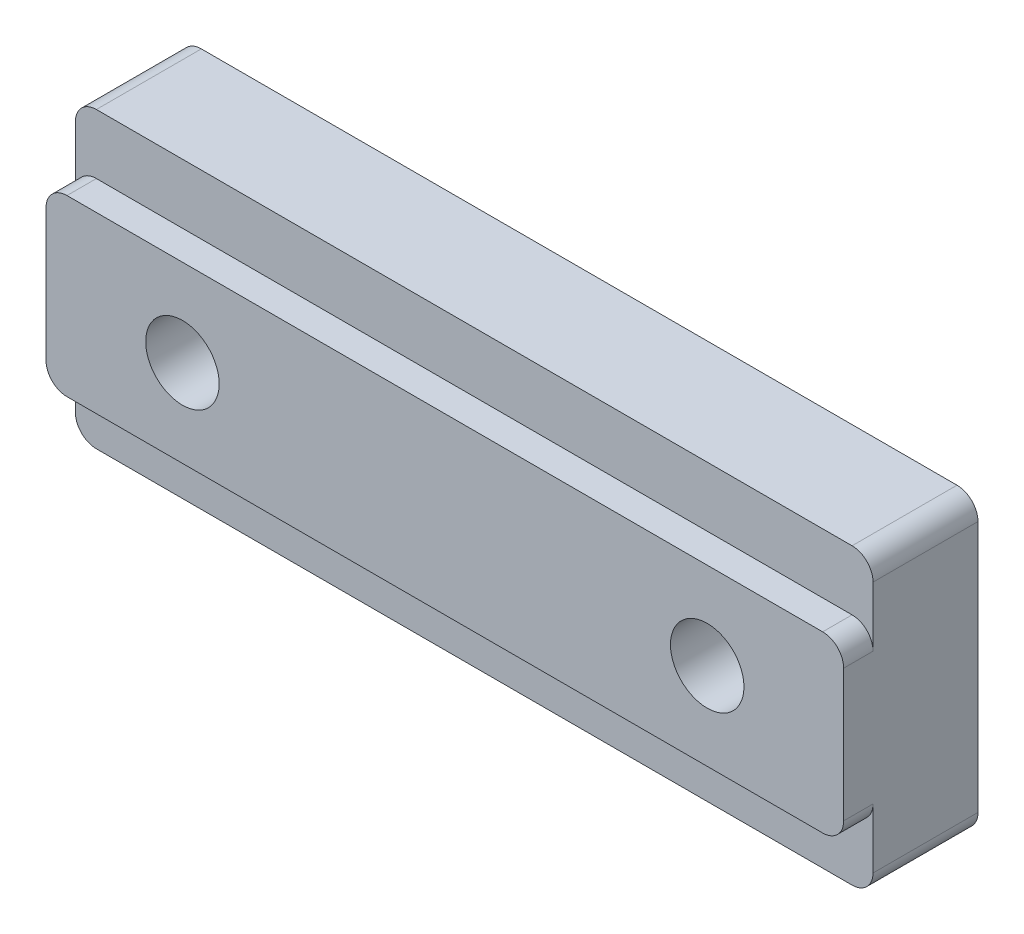
SolidWorks part; units mm, degrees
ref_plane "Спереди" through (0, 0, 0) normal (0, 0, 1) x (1, 0, 0)
ref_plane "Сверху" through (0, 0, 0) normal (0, 1, 0) x (1, 0, 0)
ref_plane "Справа" through (0, 0, 0) normal (1, 0, 0) x (0, 0, -1)
sketch "Эскиз1" plane through (0, 0, 0) normal (0, 0, 1) x (1, 0, 0)
  line L0 (-25.5909, 0) -> (25.8391, 0) construction
  line L1 (-19, -7) -> (19, -7)
  line L2 (-19, -7) -> (-19, 7)
  line L3 (-19, 7) -> (19, 7)
  line L4 (19, -7) -> (19, 7)
  line L5 (-19, -7) -> (19, 7) construction
  line L6 (-19, 7) -> (19, -7) construction
  line L7 (0, 11.0918) -> (0, -11.9823) construction
  line L9 (-19, -4.15) -> (19, -4.15)
  line L10 (-19, -4.15) -> (-19, 4.15)
  line L11 (-19, 4.15) -> (19, 4.15)
  line L12 (19, -4.15) -> (19, 4.15)
  line L13 (-19, -4.15) -> (19, 4.15) construction
  line L14 (-19, 4.15) -> (19, -4.15) construction
  circle A0 centre (-12.5, 0) radius 1.75
  circle A1 centre (12.5, 0) radius 1.75
  point P0 (0, 0)
  point P14 (0, 0)
  dimension "D1" = 12.5
  dimension "D3" = 3.5
  dimension "D4" = 3.5
  dimension "D2" = 8.3
extrude "Бобышка-Вытянуть1" add sketch "Эскиз1" along normal blind 5 contours L9 L2 L1 L4 | L11 L2 L9 L4 A0 A1 | L2 L11 L4 L3 region at (0, -5.575, 0) region at (0, 0, 0) region at (0, 5.575, 0)
extrude "Бобышка-Вытянуть2" add sketch "Эскиз1<3>" along normal blind 6.4 contours L11 L2 L9 L4 A0 A1 region at (0, 0, 0)
sketch "Эскиз1<3>" plane through (0, 0, 0) normal (0, 0, 1) x (1, 0, 0) same geometry as "Эскиз1"
sketch "Эскиз2" plane through (0, 0, 0) normal (0, 0, -1) x (-1, 0, 0)
  line L0 (0, 9.4717) -> (0, -10.1572) construction
  line L1 (-12.5, 3.3486) -> (-15.4, 1.6743)
  line L2 (-15.4, 1.6743) -> (-15.4, -1.6743)
  line L3 (-15.4, -1.6743) -> (-12.5, -3.3486)
  line L4 (-12.5, -3.3486) -> (-9.6, -1.6743)
  line L5 (-9.6, -1.6743) -> (-9.6, 1.6743)
  line L6 (-9.6, 1.6743) -> (-12.5, 3.3486)
  line L7 (9.6, 1.6743) -> (12.5, 3.3486)
  line L8 (9.6, -1.6743) -> (9.6, 1.6743)
  line L9 (12.5, -3.3486) -> (9.6, -1.6743)
  line L10 (15.4, -1.6743) -> (12.5, -3.3486)
  line L11 (15.4, 1.6743) -> (15.4, -1.6743)
  line L12 (12.5, 3.3486) -> (15.4, 1.6743)
  circle A0 centre (-12.5, 0) radius 2.9 construction
  circle A1 centre (12.5, 0) radius 2.9 construction
extrude "Вырез-Вытянуть1" cut sketch "Эскиз2" against normal blind 2.5
fillet "Скругление1" radius 1 8 edges at (-19, -7, 2.5) (-19, -4.15, 5.7) (-19, 4.15, 5.7) (-19, 7, 2.5) (19, -7, 2.5) (19, -4.15, 5.7) (19, 4.15, 5.7) (19, 7, 2.5)
chamfer "Фаска1" distance 1.3 angle 50 2 edges at (-10.75, 0, 2.5) (10.75, 0, 2.5) first distance on face at (-10.75, 0, 2.5) first distance on face at (14.25, 0, 6.4)
